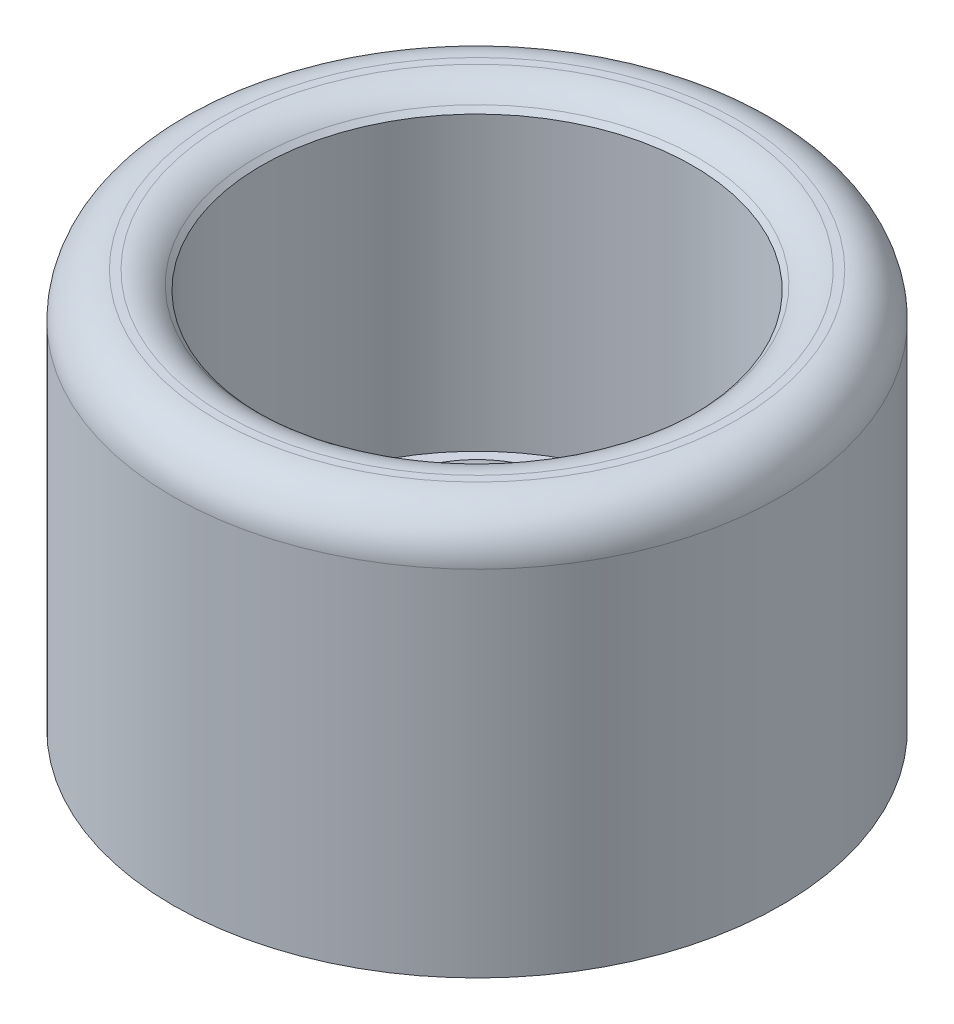
SolidWorks part; units mm, degrees
ref_plane "Front Plane" through (0, 0, 0) normal (0, 0, 1) x (1, 0, 0)
ref_plane "Top Plane" through (0, 0, 0) normal (0, 1, 0) x (1, 0, 0)
ref_plane "Right Plane" through (0, 0, 0) normal (1, 0, 0) x (0, 0, -1)
sketch "Sketch1" plane through (0, 0, 0) normal (0, 1, 0) x (1, 0, 0)
  circle A0 centre (0, 0) radius 24.384
  circle A1 centre (0, 0) radius 34.384
  dimension "D1" = 48.768
  dimension "D2" = 10
extrude "Boss-Extrude1" add sketch "Sketch1" along normal blind 35
extrude "Boss-Extrude2" add sketch "Sketch1<3>" against normal blind 10 contours A1 A0 | A0 region at (-33.4115, 0, 0)
sketch "Sketch1<3>" plane through (0, 0, 0) normal (0, 1, 0) x (1, 0, 0) same geometry as "Sketch1"
sketch "Sketch3" plane through (0, 0, 0) normal (0, 1, 0) x (1, 0, 0)
  circle A0 centre (0, 0) radius 12.5
  dimension "D1" = 25
extrude "Boss-Extrude3" add sketch "Sketch3" along normal blind 10
fillet "Fillet1" radius 5 2 edges at (0, 10, 12.5) (0, 0, 12.5)
hole_wizard "Ø12.0mm Dowel Hole1" positions "Sketch4" profile "Sketch6" hole size "Ø12.0" standard "ANSI Metric"
sketch "Sketch4" plane through (0, -10, 0) normal (0, -1, 0) x (-1, 0, 0)
  point P0 (0, 0)
sketch "Sketch6" plane through (0, -10, 0) normal (1, 0, 0) x (0, 0, -1)
  line L0 (0, 0) -> (0, 10)
  line L1 (0, 10) -> (5.5, 10)
  line L2 (5.5, 10) -> (5.5, 0)
  line L5 (5.5, 0) -> (0, 0)
  line L10 (0, 10) -> (-5.5, 10) construction
  line L11 (0, -6.35) -> (0, 107.95) construction
  dimension "Hole Dia." = 11
  dimension "Hole Depth" = 10
  dimension "Drill Angle" = 180
hole_wizard "Ø8.0mm Dowel Hole2" positions "Sketch7" profile "Sketch9" hole size "Ø8.0" standard "ANSI Metric" end condition through all
sketch "Sketch7" plane through (0, 0, 0) normal (0, -1, 0) x (-1, 0, 0)
  point P0 (0, 0)
sketch "Sketch9" plane through (0, 0, 0) normal (1, 0, 0) x (0, 0, -1)
  line L0 (0, 0) -> (0, 35)
  line L1 (0, 35) -> (4.5, 35)
  line L2 (4.5, 35) -> (4.5, 0)
  line L5 (4.5, 0) -> (0, 0)
  line L11 (0, -6.35) -> (0, 107.95) construction
  dimension "Thru Hole Dia." = 9
  dimension "Thru Hole Depth" = 35
chamfer "Chamfer1" distance 2 angle 45 1 edges at (0, 35, 24.384)
chamfer "Chamfer2" distance 0.5 angle 45 1 edges at (0, -10, -5.5)
chamfer "Chamfer4" distance 0.5 2 edges at (0, 0, -5.5) (0, 0, -4.5)
fillet "Fillet2" radius 5 2 edges at (0, 35, 34.384) (0, 35, 26.384)
